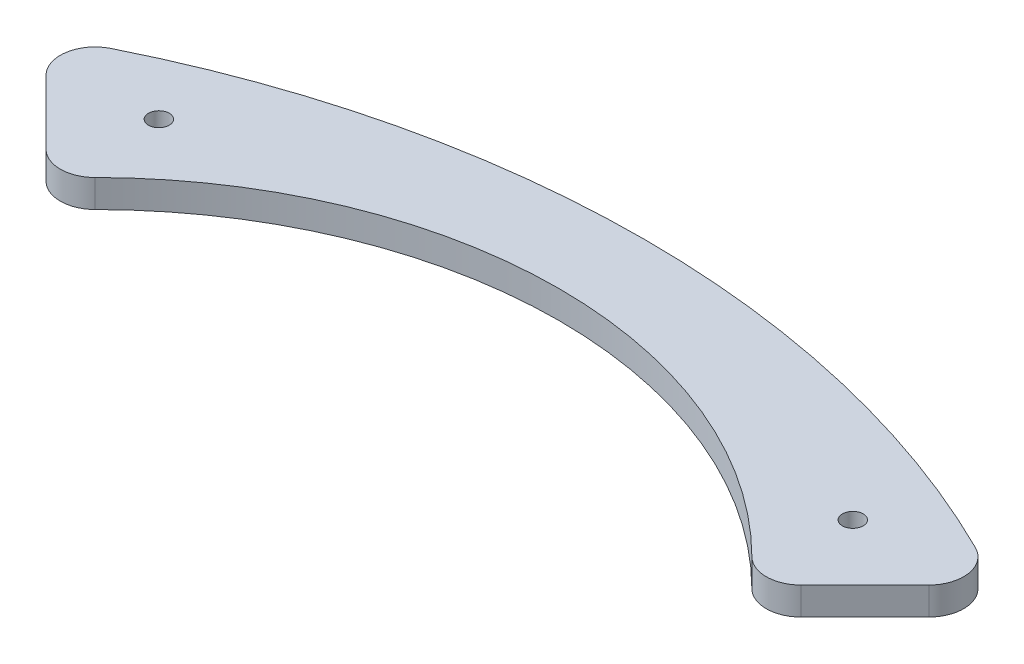
SolidWorks part; units mm, degrees
material "PMMA"
ref_plane "Front Plane" through (0, 0, 0) normal (0, 0, 1) x (1, 0, 0)
ref_plane "Top Plane" through (0, 0, 0) normal (0, 1, 0) x (1, 0, 0)
ref_plane "Right Plane" through (0, 0, 0) normal (1, 0, 0) x (0, 0, -1)
sketch "Sketch1" plane through (0, 0, 0) normal (0, 1, 0) x (1, 0, 0)
  line L0 (-68.4085, 122.1486) -> (-50.7308, 104.4709)
  line L1 (68.4085, 122.1486) -> (50.7308, 104.4709)
  line L3 (0, 0) -> (-117.9329, 117.9329) construction
  line L4 (0, 0) -> (118.2874, 118.2874) construction
  line L5 (0, 0) -> (0, 174.1104) construction
  line L6 (-15, 127.1181) -> (15, 127.1181) construction
  line L7 (-15, 127.1181) -> (-15, 116.1181) construction
  line L8 (-15, 116.1181) -> (15, 116.1181) construction
  line L9 (15, 127.1181) -> (15, 116.1181) construction
  arc A0 (-68.4085, 122.1486) -> (68.4085, 122.1486) centre (0, 0) cw
  arc A1 (-50.7308, 104.4709) -> (50.7308, 104.4709) centre (0, 60.7058) cw
  circle A2 centre (0, 0) radius 128 construction
  dimension "D1" = 140
  dimension "D6" = 67
  dimension "D7" = 12
  dimension "D2" = 25
  dimension "D3" = 45
  dimension "D4" = 38
  dimension "D5" = 38
  dimension "D8" = 11
  dimension "D9" = 30
extrude "Boss-Extrude1" add sketch "Sketch1" along normal blind 4
fillet "Fillet1" radius 5 4 edges at (68.4085, 2, -122.1486) (50.7308, 2, -104.4709) (-68.4085, 2, -122.1486) (-50.7308, 2, -104.4709)
sketch "Sketch2" plane through (0, 4, 0) normal (0, 1, 0) x (1, 0, 0)
  circle A0 centre (-50, 120) radius 1.5
  circle A1 centre (50, 120) radius 1.5
  dimension "D1" = 3
  dimension "D2" = 120
  dimension "D3" = 50
  dimension "D4" = 50
extrude "Cut-Extrude1" cut sketch "Sketch2" against normal up to next
